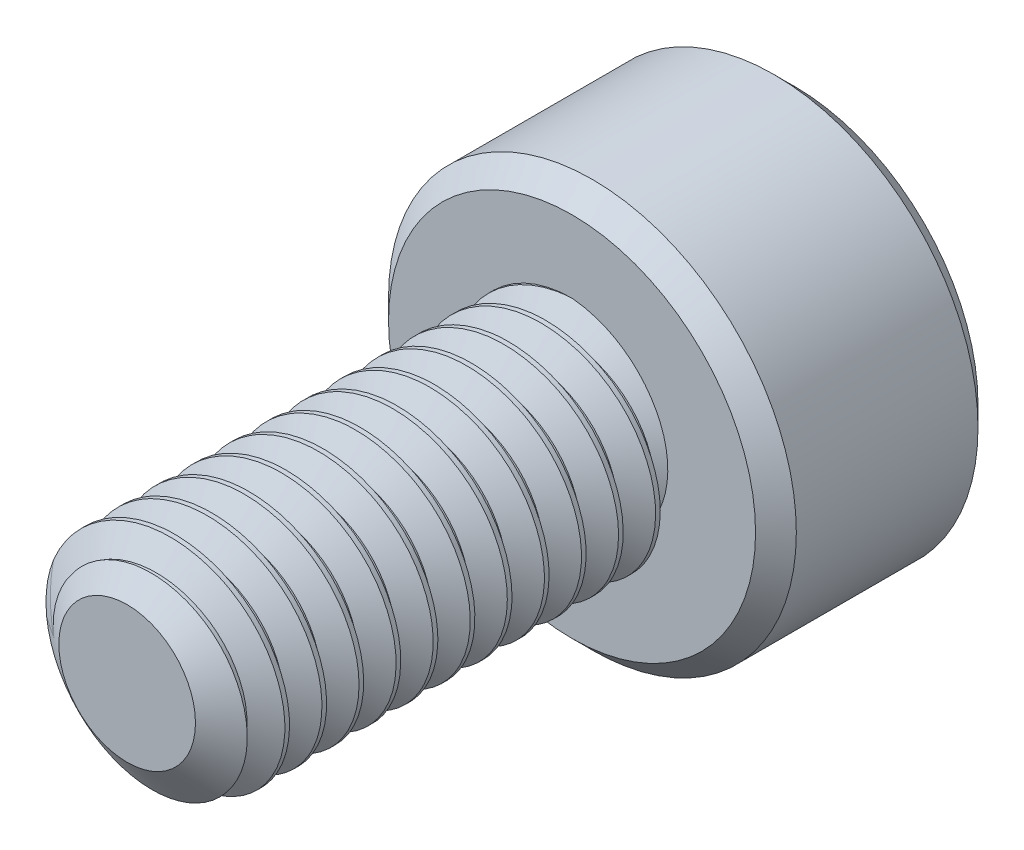
SolidWorks part; units mm, degrees
note: '?' marks a value the reader was unsure of.
other "DetailItem1"
ref_plane "Front Plane" through (0, 0, 0) normal (0, 0, 1) x (1, 0, 0)
ref_plane "Top Plane" through (0, 0, 0) normal (0, 1, 0) x (1, 0, 0)
ref_plane "Right Plane" through (0, 0, 0) normal (1, 0, 0) x (0, 0, -1)
sketch "Sketch1" plane through (0, 0, 0) normal (0, 0, 1) x (1, 0, 0)
  circle A0 centre (0, 0) radius 1.5
  dimension "OD" = 3
extrude "Extrude1" add sketch "Sketch1" against normal blind 6
sketch "Sketch2" plane through (0, 0, 0) normal (0, 0, 1) x (1, 0, 0)
  circle A0 centre (0, 0) radius 1.5 construction
  circle A1 centre (0, 0) radius 1.5
curve "Helix/Spiral1" pitch 0.5 height 6.5 radius 1.5 centre (0, 0, 0) axis (0, 0, -1) start towards (0, 1, 0) parameters "pitch"=0.5
sketch "Sketch3" plane through (0, 0, 0) normal (1, 0, 0) x (0, 0, -1)
  line L0 (-0.4375, 1.5) -> (-0.25, 1.1752)
  line L1 (-0.25, 1.1752) -> (-0.1875, 1.1752)
  line L2 (-0.1875, 1.1752) -> (0, 1.5)
  line L3 (-0.4375, 1.5) -> (0, 1.5)
  line L4 (-0.2187, 1.5) -> (-0.2188, 1.1752) construction
  line L5 (-0.3438, 1.3376) -> (-0.0938, 1.3376) construction
  line L6 (0, 1.5) -> (0, -1.5) construction
  dimension "D1" = 0.0625
  dimension "D2" = 0.25
  dimension "D3" = 60
sweep "Cut-Sweep1" cut profiles "Sketch3" path "Helix/Spiral1" align with end faces yes
sketch "Sketch4" plane through (0, 0, 0) normal (1, 0, 0) x (0, 0, -1)
  line L0 (0.4053, 1.5) -> (0, 0.9212)
  line L1 (0, 0.9212) -> (0, 1.5)
  line L2 (0.4053, 1.5) -> (0, 1.5)
  line L3 (-0.4375, 1.5) -> (0, 1.5) construction
  line L4 (0, 0) -> (7.0209, 0) construction
  dimension "D1" = 55
  dimension "D2" = 0.254
revolve "Cut-Revolve1" cut sketch "Sketch4" angle 360 about L4
sketch "Sketch6" plane through (0, 0, -6) normal (0, 0, -1) x (-1, 0, 0)
  circle A0 centre (0, 0) radius 2.75
  dimension "head dia" = 5.5
extrude "Extrude2" add sketch "Sketch6" along normal blind 3
sketch "Sketch7" plane through (0, 0, -9) normal (0, 0, -1) x (-1, 0, 0)
  line L1 (0, 1.4434) -> (-1.25, 0.7217)
  line L2 (-1.25, 0.7217) -> (-1.25, -0.7217)
  line L3 (-1.25, -0.7217) -> (0, -1.4434)
  line L4 (0, -1.4434) -> (1.25, -0.7217)
  line L5 (1.25, -0.7217) -> (1.25, 0.7217)
  line L6 (1.25, 0.7217) -> (0, 1.4434)
  circle A0 centre (0, 0) radius 1.25 construction
  dimension "hex dia" = 2.5
extrude "Cut-Extrude1" cut sketch "Sketch7" against normal blind 1.875
sketch "Sketch8" plane through (0, 0, -9) normal (0, 0, -1) x (-1, 0, 0)
  circle A0 centre (0, 0) radius 1.4434
extrude "Cut-Extrude2" cut sketch "Sketch8" against normal through all draft 45
chamfer "Chamfer1" distance 0.275 angle 45 2 edges at (-2.75, 0, -9) (-2.75, 0, -6)
sketch "Sketch10" plane through (0, 0, -6) normal (0, 0, 1) x (1, 0, 0)
  circle A1 centre (0, 0) radius 1.5
  circle A2 centre (0, 0) radius 1.5
  dimension "D1" = 0
ref_plane "Plane1" through (0, 0, 0) normal (0, 0, 1) x (1, 0, 0)
extrude "partial thread" [suppressed] add sketch "Sketch10" along normal up to surface (4 mm away) separate body
chamfer "Chamfer2" [suppressed] distance 0.06 angle 45
combine bodies "Combine1" [suppressed] operation type? add bodies to combine 107 108
sketch "Sketch9" plane through (0, 0, 0) normal (1, 0, 0) x (0, 0, -1)
  line L0 (0, 1.5) -> (0, -1.5) construction
  line L1 (1.25, 1.5) -> (1.25, -1.5) construction
  dimension "D1" = 1.25
equation "\"D3@Helix/Spiral1\" = \"screw length@Extrude1\"+\"pitch@Helix/Spiral1\""
equation "\"D1@Sketch3\" = \"pitch@Helix/Spiral1\"*.125"
equation "\"D2@Sketch3\" = \"pitch@Helix/Spiral1\"*.5"
equation "\"D1@Cut-Extrude1\" = \"hex dia@Sketch7\"*.75"
equation "\"D1@Chamfer1\" = \"head dia@Sketch6\"*.05"
equation "\"D1@Sketch9\" = \"pitch@Helix/Spiral1\"*2.5"
equation "\"D1@Chamfer2\"=\"OD@Sketch1\"*.02"
